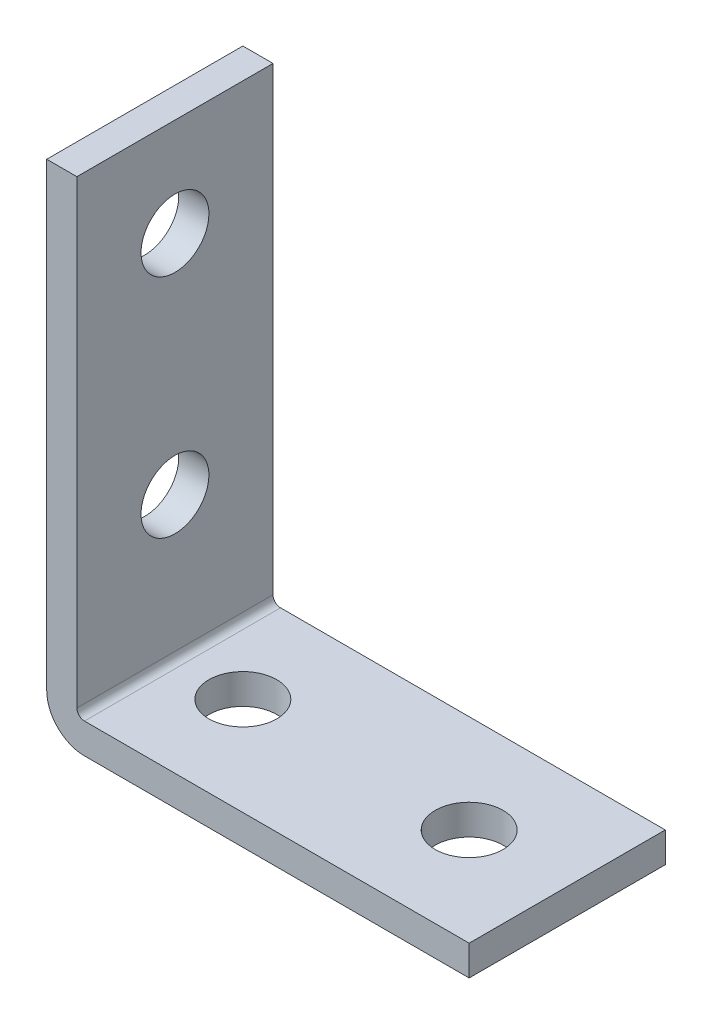
SolidWorks part; units mm, degrees
ref_plane "Front Plane" through (0, 0, 0) normal (0, 0, 1) x (1, 0, 0)
ref_plane "Top Plane" through (0, 0, 0) normal (0, 1, 0) x (1, 0, 0)
ref_plane "Right Plane" through (0, 0, 0) normal (1, 0, 0) x (0, 0, -1)
sketch "Sketch1" plane through (0, 0, 0) normal (0, 0, 1) x (1, 0, 0)
  line L0 (0, 104.775) -> (0, 7.9375)
  line L1 (7.9375, 0) -> (88.9, 0)
  arc A0 (0, 7.9375) -> (7.9375, 0) centre (7.9375, 7.9375) ccw
  dimension "D1" = 7.9375
  dimension "B" = 88.9
  dimension "A" = 104.775
extrude "Extrude-Thin1" add sketch "Sketch1" along normal mid plane 41.275 thin thin type one direction reverse wall 6.35
sketch "Sketch2" plane through (0, 6.35, 0) normal (0, 1, 0) x (1, 0, 0)
  line L0 (88.9, -20.6375) -> (88.9, 20.6375) construction
  circle A0 centre (68.2625, 0) radius 7.1438
  circle A1 centre (20.6375, 0) radius 7.1437
  dimension "Hole Size" = 14.2875
  dimension "edge" = 20.6375
  dimension "Spacing" = 47.625
extrude "Cut-Extrude1" cut sketch "Sketch2" against normal through all
sketch "Sketch3" plane through (6.35, 0, 0) normal (1, 0, 0) x (0, 0, -1)
  line L0 (-20.6375, 104.775) -> (20.6375, 104.775) construction
  circle A0 centre (0, 84.1375) radius 7.1438
  circle A1 centre (0, 36.5125) radius 7.1438
  dimension "D2" = 14.2875
  dimension "D1" = 20.6375
  dimension "D3" = 47.625
extrude "Cut-Extrude2" cut sketch "Sketch3" against normal through all
equation "\"D3@Sketch3\" = \"Spacing@Sketch2\""
equation "\"D2@Sketch3\" = \"Hole Size@Sketch2\""
